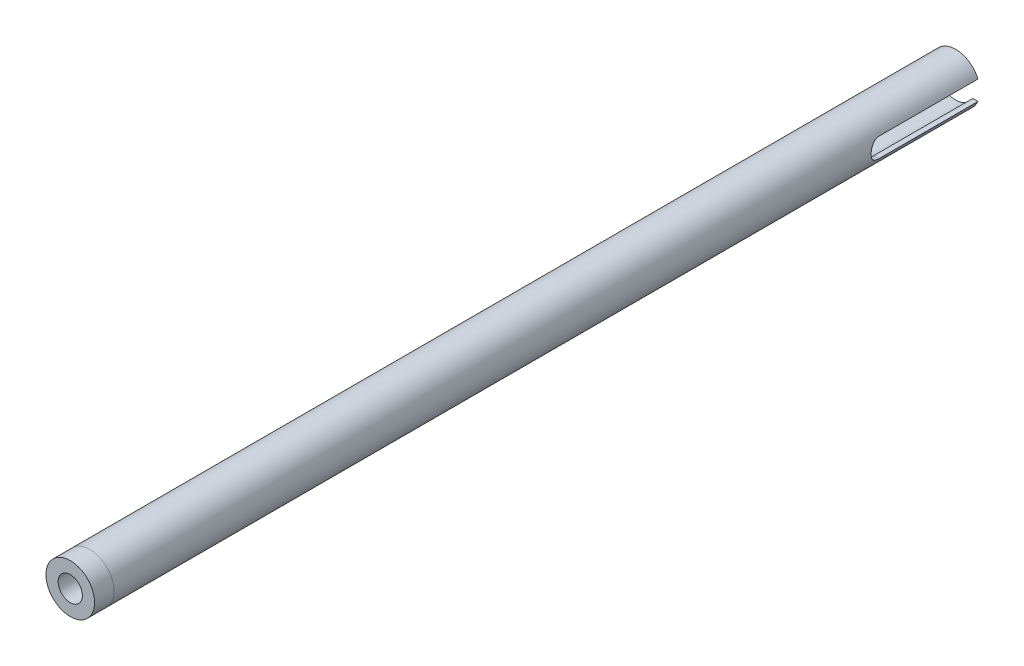
SolidWorks part; units mm, degrees
ref_plane "Front Plane" through (0, 0, 0) normal (0, 0, 1) x (1, 0, 0)
ref_plane "Top Plane" through (0, 0, 0) normal (0, 1, 0) x (1, 0, 0)
ref_plane "Right Plane" through (0, 0, 0) normal (1, 0, 0) x (0, 0, -1)
sketch "Axis" plane through (0, 0, 0) normal (0, 1, 0) x (1, 0, 0)
  line L0 (0, 0) -> (0, 289.2051) construction
  line L1 (0, 0) -> (0, -34.925) construction
  line L2 (0, 289.2051) -> (-7.9375, 289.2051) construction
  line L3 (0, 315.4109) -> (-28.3474, 221.8217) construction
  dimension "D1" = 34.925
  dimension "D2" = 7.9375
sketch "Sketch1" plane through (0, 0, 0) normal (0, 0, 1) x (1, 0, 0)
  line L0 (-7.9375, 0) -> (7.9375, 0) construction
  line L1 (-7.2748, 3.175) -> (7.2748, 3.175)
  line L2 (-7.2748, -3.175) -> (7.2748, -3.175)
  circle A0 centre (0, 0) radius 7.9375
  circle A1 centre (0, 0) radius 6.4135
  circle A2 centre (0, 0) radius 3.9688
  dimension "D1" = 15.875
  dimension "D3" = 7.9375
  dimension "D2" = 1.524
  dimension "D4" = 6.35
extrude "Threaded insert 1-1" add sketch "Sketch1" against normal blind 6.35 contours A2 L1 A1 | A1 L1 A0 | A2 L0 A1 L1 | A1 L0 A0 L1 | L0 A1 L2 A0 | L0 A2 L2 A1 | A2 L2 A1 | A1 L2 A0 | L0 A1 L2 A2 | L0 A0 L2 A1 | A0 L0 A1 L1 | A1 L0 A2 L1 region at (4.7887, 1.6543, 0) region at (4.7887, -1.6543, 0) region at (6.9234, 1.6163, 0) region at (6.9234, -1.6163, 0) region at (-4.7887, -1.6543, 0) region at (-4.7887, 1.6543, 0) region at (0, 4.6159, 0) region at (0, -4.6159, 0) region at (0, 6.5666, 0) region at (6.4237, -3.3281, 0) region at (-6.9234, -1.6163, 0) region at (-6.9234, 1.6163, 0)
extrude "Threaded insert 1-2" add sketch "Sketch1<3>" against normal blind 9.525 from surface contours A2 L1 A1 | A2 L0 A1 L1 | L0 A2 L2 A1 | A2 L2 A1 | L0 A1 L2 A2 | A1 L0 A2 L1 region at (4.7887, 1.6543, 0) region at (4.7887, -1.6543, 0) region at (-4.7887, -1.6543, 0) region at (-4.7887, 1.6543, 0) region at (0, 4.6159, 0) region at (0, -4.6159, 0) starting at face at (7.9375, 0, -6.35)
sketch "Sketch1<3>" plane through (0, 0, 0) normal (0, 0, 1) x (1, 0, 0) same geometry as "Sketch1"
extrude "A-arm tube" add sketch "Sketch1<4>" against normal up to vertex (289.2051 mm away) from surface separate body contours A1 L1 A0 | A1 L0 A0 L1 | L0 A1 L2 A0 | A1 L2 A0 | L0 A0 L2 A1 | A0 L0 A1 L1 region at (6.9234, 1.6163, 0) region at (6.9234, -1.6163, 0) region at (0, 6.5666, 0) region at (6.4237, -3.3281, 0) region at (-6.9234, -1.6163, 0) region at (-6.9234, 1.6163, 0) up to point (0, 0, -289.2051) starting at face at (6.4135, 0, -6.35)
sketch "Sketch1<4>" plane through (0, 0, 0) normal (0, 0, 1) x (1, 0, 0) same geometry as "Sketch1"
extrude "Apex slot" cut sketch "Sketch1<5>" along normal blind 35.56 from surface contours A0 L0 A1 L1 | L0 A0 L2 A1 | A1 L0 A0 L1 | L0 A1 L2 A0 region at (6.9234, 1.6163, 0) region at (6.9234, -1.6163, 0) region at (-6.9234, -1.6163, 0) region at (-6.9234, 1.6163, 0) starting at face at (6.4135, 0, -289.2051)
sketch "Sketch1<5>" plane through (0, 0, 0) normal (0, 0, 1) x (1, 0, 0) same geometry as "Sketch1"
fillet "Fillet1" radius 3.175 4 edges at (-6.4237, 3.175, -253.6451) (-6.4237, -3.175, -253.6451) (6.4237, -3.175, -253.6451) (6.4237, 3.175, -253.6451)
equation "\"tube diameter\"= 5 / 8"
equation "\"tube thickness\"= .06"
equation "\"apex thickness\"= .25"
equation "\"tube slot\"= 1.4"
equation "\"D1@Sketch1\"=\"tube diameter\""
equation "\"D2@Sketch1\"=\"tube thickness\""
equation "\"threaded insert hole\"= .3125"
equation "\"D3@Sketch1\"=\"threaded insert hole\""
equation "\"D4@Sketch1\"=\"apex thickness\""
equation "\"D1@Apex slot\" = \"tube slot\""
equation "\"D1@Fillet1\"=\"apex thickness\"/2"
equation "\"D2@Axis\"=\"tube diameter\"/2"
